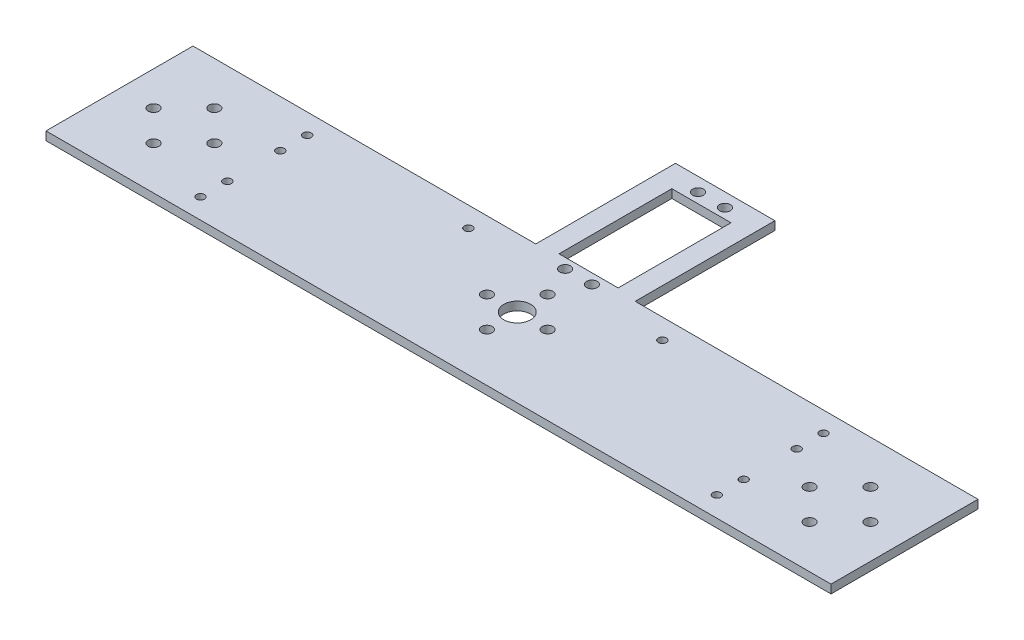
SolidWorks part; units mm, degrees
ref_plane "Front" through (0, 0, 0) normal (0, 0, 1) x (1, 0, 0)
ref_plane "Top" through (0, 0, 0) normal (0, 1, 0) x (1, 0, 0)
ref_plane "Right" through (0, 0, 0) normal (1, 0, 0) x (0, 0, -1)
sketch "Sketch1" plane through (0, 0, 0) normal (0, 1, 0) x (1, 0, 0)
  line L0 (0, -25.4) -> (292.2, -25.4)
  line L1 (0, 0) -> (292.2, 0)
  line L2 (0, 0) -> (0, -50.8)
  line L3 (0, -50.8) -> (292.2, -50.8)
  line L4 (292.2, 0) -> (292.2, -50.8)
  line L7 (115.2643, 0) -> (138.7357, 0)
  line L9 (146.1, -25.4) -> (146.1, 32.2)
  line L10 (146.1, 32.2) -> (146.1, 46.8974)
  line L11 (141.1, 46.8974) -> (151.1, 46.8974)
  line L12 (141.1, -2.6026) -> (151.1, -2.6026)
  line L13 (127.6, 0) -> (127.6, 52)
  line L14 (127.6, 52) -> (164.6, 52)
  line L15 (164.6, 52) -> (164.6, 0)
  line L16 (146.1, -2.6026) -> (146.1, 46.8974)
  line L17 (135.1, 22.1474) -> (157.1, 22.1474)
  line L18 (135.1, 1.1474) -> (135.1, 43.1474)
  line L19 (135.1, 1.1474) -> (157.1, 1.1474)
  line L20 (157.1, 1.1474) -> (157.1, 43.1474)
  line L21 (157.1, 43.1474) -> (135.1, 43.1474)
  line L22 (0, -50.8) -> (292.2, -50.8)
  line L23 (0, -50.8) -> (0, -54.7137)
  line L24 (292.2, -50.8) -> (292.2, -54.7137)
  line L25 (0, -54.7137) -> (292.2, -54.7137)
  circle A0 centre (146.1, -25.4) radius 11.3137
  circle A1 centre (146.1, -36.7137) radius 2
  circle A2 centre (157.4137, -25.4) radius 2
  circle A3 centre (146.1, -14.0863) radius 2
  circle A4 centre (134.7863, -25.4) radius 2
  circle A5 centre (146.1, -25.4) radius 5
  circle A6 centre (141.1, -2.6026) radius 2
  circle A7 centre (151.1, -2.6026) radius 2
  circle A8 centre (141.1, 46.8974) radius 2
  circle A9 centre (151.1, 46.8974) radius 2
  point P25 (146.1, 46.8974)
  point P28 (146.1, -2.6026)
  point P40 (146.1, 22.1474)
  point P43 (135.1, 22.1474)
  dimension "D3" = 57.6
  dimension "D8" = 37
  dimension "D13" = 18
  dimension "D14" = 22.6274
  dimension "D1" = 292.2
  dimension "D2" = 50.8
  dimension "D4" = 10
  dimension "D5" = 10
  dimension "D6" = 49.5
  dimension "D7" = 14.6974
  dimension "D9" = 18.5
  dimension "D10" = 22
  dimension "D11" = 42
  dimension "D12" = 52
extrude "Boss-Extrude1" add sketch "Sketch1" along normal blind 3.175 contours A4 L0 L2 L3 L4 A2 A0 A1 | A6 L9 L1 L2 L0 A4 A0 A3 | A7 L9 A3 A0 A2 L0 L4 L1 L7 | A9 L7 L1 L15 L14 L13 A8 | A5 L0 A4 A0 A1 A2 | A5 L0 A2 A0 A3 L9 | A5 L9 A3 A0 A4 L0 | L23 L25 L24 L3 region at (151.5378, 0, 19.9622) region at (146.1, 0, 30.8378) region at (140.6622, 0, 19.9622) region at (221.4194, 0, 12.503) region at (160.7442, 0, 29.0391) region at (70.7806, 0, 12.503) region at (146.1, 0, 52.7569) region at (142.4179, 0, -0.6382)
sketch "Sketch2" plane through (0, 0, 0) normal (0, -1, 0) x (1, 0, 0)
  line L0 (50, 54.7137) -> (50, 0)
  line L1 (0, 54.7137) -> (292.2, 54.7137) construction
  line L2 (0, 0) -> (127.6, 0) construction
  line L3 (50, 7.5) -> (137.5197, 7.5)
  line L4 (50, 47.2137) -> (153.3965, 47.2137)
  line L5 (0, 0) -> (0, 54.7137) construction
  line L6 (146.1, 47.2137) -> (146.1, 7.5)
  circle A0 centre (50, 47.2137) radius 1.5
  circle A1 centre (50, 7.5) radius 1.5
  circle A2 centre (110, 7.5) radius 1.5
  circle A3 centre (182.2, 7.5) radius 1.5
  circle A4 centre (242.2, 7.5) radius 1.5
  circle A5 centre (242.2, 47.2137) radius 1.5
  circle A6 centre (50, 37.2137) radius 1.5
  circle A7 centre (50, 17.5) radius 1.5
  circle A8 centre (242.2, 37.2137) radius 1.5
  circle A9 centre (242.2, 17.5) radius 1.5
  dimension "D2" = 7.5
  dimension "D4" = 60
  dimension "D5" = 10
  dimension "D1" = 50
  dimension "D3" = 7.5
  dimension "D6" = 10
extrude "Cut-Extrude1" cut sketch "Sketch2" against normal blind 10 contours A0 | A5 | A1 | A2 | A3 | A4 | A6 | A7 | A8 | A9
sketch "Sketch3" plane through (0, 0, 0) normal (0, -1, 0) x (1, 0, 0)
  line L0 (0, 27.3569) -> (24, 27.3569)
  line L1 (0, 0) -> (0, 54.7137) construction
  line L2 (146.1, 30.4) -> (146.1, 20.4)
  circle A0 centre (24, 27.3569) radius 11.3137
  circle A1 centre (24, 38.6706) radius 2
  circle A2 centre (12.6863, 27.3569) radius 2
  circle A3 centre (35.3137, 27.3569) radius 2
  circle A4 centre (24, 16.0431) radius 2
  circle A5 centre (146.1, 25.4) radius 5 construction
  circle A6 centre (268.2, 16.0431) radius 2
  circle A7 centre (279.5137, 27.3569) radius 2
  circle A8 centre (268.2, 38.6706) radius 2
  circle A9 centre (256.8863, 27.3569) radius 2
  dimension "D1" = 24
extrude "Cut-Extrude2" cut sketch "Sketch3" against normal blind 10 contours A2 | A1 | A3 | A4 | A9 | A8 | A7 | A6
